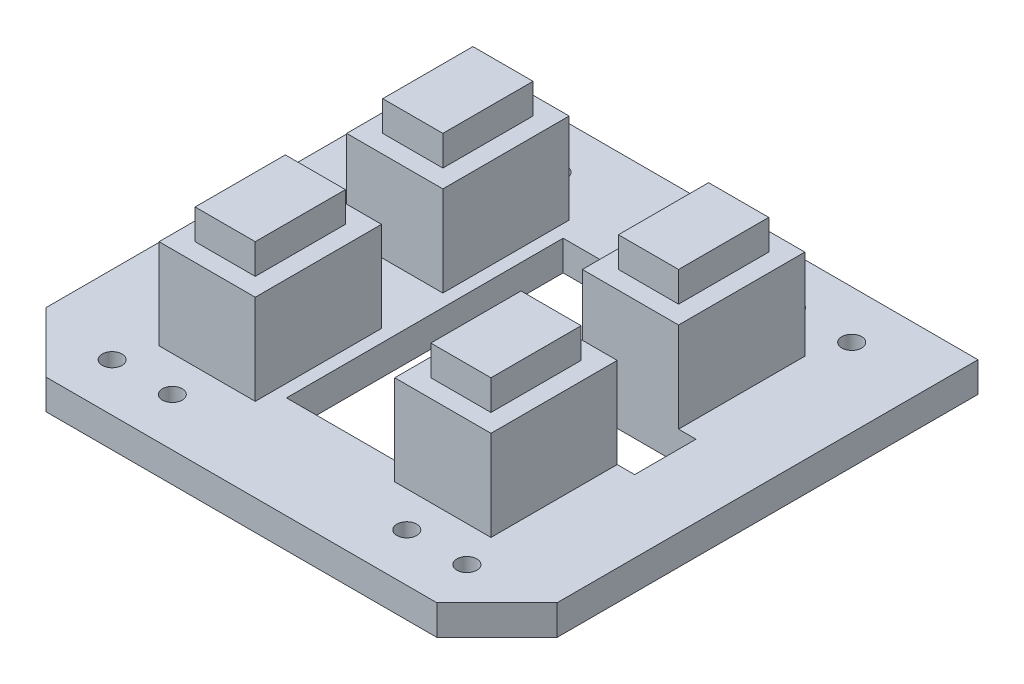
SolidWorks part; units mm, degrees
material "PLA+ esun"
ref_plane "Front Plane" through (0, 0, 0) normal (0, 0, 1) x (1, 0, 0)
ref_plane "Top Plane" through (0, 0, 0) normal (0, 1, 0) x (1, 0, 0)
ref_plane "Right Plane" through (0, 0, 0) normal (1, 0, 0) x (0, 0, -1)
sketch "Sketch1" plane through (0, 0, 0) normal (0, 1, 0) x (1, 0, 0)
  line L0 (0, 0) -> (49.8029, 0) construction
  line L1 (-77.5, 77.5) -> (77.5, 77.5)
  line L2 (-77.5, 77.5) -> (-77.5, -77.5)
  line L3 (-77.5, -77.5) -> (77.5, -77.5)
  line L4 (77.5, 77.5) -> (77.5, -77.5)
  line L5 (-77.5, 77.5) -> (77.5, -77.5) construction
  line L6 (-77.5, -77.5) -> (77.5, 77.5) construction
  line L7 (-9.5, 23) -> (9.5, 23)
  line L8 (-9.5, 23) -> (-9.5, -23)
  line L9 (-9.5, -23) -> (9.5, -23)
  line L10 (9.5, 23) -> (9.5, -23)
  line L11 (-9.5, 23) -> (9.5, -23) construction
  line L12 (-9.5, -23) -> (9.5, 23) construction
  line L14 (0, 0) -> (0, 35.7746) construction
  line L17 (-77.5, -77.5) -> (-42.5, -77.5)
  line L18 (-77.5, -77.5) -> (-77.5, -24.25)
  line L19 (-77.5, -24.25) -> (-42.5, -24.25)
  line L20 (-42.5, -77.5) -> (-42.5, -24.25)
  line L21 (-77.5, 24.25) -> (-42.5, 24.25)
  line L22 (-42.5, 77.5) -> (-42.5, 24.25)
  line L23 (42.5, -77.5) -> (42.5, -24.25)
  line L24 (77.5, -24.25) -> (42.5, -24.25)
  line L25 (42.5, 77.5) -> (42.5, 24.25)
  line L26 (77.5, 24.25) -> (42.5, 24.25)
  line L27 (20, -40) -> (42.5, -40)
  line L28 (-42.5, 24.25) -> (-77.5, 24.25)
  line L29 (-42.5, 24.25) -> (-42.5, -24.25)
  line L30 (-42.5, -24.25) -> (-77.5, -24.25)
  line L31 (-77.5, 24.25) -> (-77.5, -24.25)
  line L32 (42.5, 24.25) -> (77.5, 24.25)
  line L33 (42.5, 24.25) -> (42.5, -24.25)
  line L34 (42.5, -24.25) -> (77.5, -24.25)
  line L35 (77.5, 24.25) -> (77.5, -24.25)
  line L36 (-42.5, 77.5) -> (42.5, 77.5)
  line L37 (-42.5, 77.5) -> (-42.5, 40)
  line L38 (-42.5, 40) -> (42.5, 40)
  line L39 (42.5, 77.5) -> (42.5, 40)
  line L40 (-42.5, -77.5) -> (42.5, -77.5)
  line L41 (-42.5, -77.5) -> (-42.5, -40)
  line L42 (-42.5, -40) -> (-20, -40)
  line L43 (42.5, -77.5) -> (42.5, -40)
  line L45 (-20, -40) -> (-20, -77.5)
  line L46 (-20, -77.5) -> (20, -77.5)
  line L47 (20, -40) -> (20, -77.5)
  line L49 (-20, -77.5) -> (20, -77.5)
  line L50 (-20, -77.5) -> (-20, -40)
  line L51 (-20, -40) -> (20, -40)
  line L52 (20, -77.5) -> (20, -40)
  circle A1 centre (29.5, 32) radius 1.65
  circle A2 centre (19.5, 32) radius 1.65
  circle A3 centre (19.5, -32) radius 1.65
  circle A4 centre (29.5, -32) radius 1.65
  circle A5 centre (-29.5, -32) radius 1.65
  circle A6 centre (-19.5, -32) radius 1.65
  circle A7 centre (-19.5, 32) radius 1.65
  circle A8 centre (-29.5, 32) radius 1.65
  point P0 (0, 0)
  point P6 (0, 0)
  point P13 (0, 0)
  dimension "D5" = 9
  dimension "D8" = 20
  dimension "D9" = 53.25
  dimension "D6" = 3.3
  dimension "D1" = 155
  dimension "D2" = 155
  dimension "D3" = 46
  dimension "D4" = 19
  dimension "D7" = 2
  dimension "D10" = 35
  dimension "D11" = 37.5
  dimension "D12" = 37.5
  dimension "D13" = 22.5
  dimension "D14" = 22.5
extrude "Boss-Extrude3" add sketch "Sketch1" along normal blind 5 contours L4 L26 L25 L1 L22 L21 L2 L19 L20 L3 L23 L24 A7 A6 A5 A3 A2 A1 L7 L10 L9 L8 A4 A8 region at (0, 0, -38.8327)
chamfer "Chamfer1" distance 10 angle 45 2 edges at (-42.5, 2.5, 40) (42.5, 2.5, 40)
sketch "Sketch6" plane through (0, 5, 0) normal (0, 1, 0) x (1, 0, 0)
  line L0 (-24.6, 8.1) -> (-14.6, 8.1)
  line L9 (-14.6, 8.1) -> (-14.6, 23.1)
  line L10 (-24.6, 8.1) -> (-24.6, 23.1)
  line L11 (-24.7, 8) -> (-14.5, 8)
  line L12 (-24.7, 23.2) -> (-14.5, 23.2)
  line L13 (-24.7, 23.2) -> (-24.7, -23.2)
  line L14 (-24.7, -23.2) -> (-14.5, -23.2)
  line L15 (-14.5, 23.2) -> (-14.5, -23.2)
  line L16 (9.5, 23) -> (-9.5, 23)
  line L17 (9.5, 23) -> (9.5, -23)
  line L18 (9.5, -23) -> (-9.5, -23)
  line L19 (-9.5, 23) -> (-9.5, -23)
  line L20 (9.5, 23) -> (-9.5, -23) construction
  line L21 (9.5, -23) -> (-9.5, 23) construction
  line L22 (-24.7, -8) -> (-14.5, -8)
  line L23 (0, 0) -> (0, -14.0514) construction
  line L24 (24.6, 23.1) -> (14.6, 23.1)
  line L29 (14.6, -8.1) -> (14.6, -23.1)
  line L30 (0, 0) -> (7.1407, 0) construction
  line L35 (-24.6, -8.1) -> (-14.6, -8.1)
  line L36 (-24.6, -8.1) -> (-24.6, -23.1)
  line L37 (-24.6, -23.1) -> (-14.6, -23.1)
  line L38 (-14.6, -8.1) -> (-14.6, -23.1)
  line L39 (-24.6, 23.1) -> (-14.6, 23.1)
  line L40 (24.6, -23.1) -> (14.6, -23.1)
  line L41 (24.6, -8.1) -> (24.6, -23.1)
  line L42 (24.6, -8.1) -> (14.6, -8.1)
  line L43 (24.7, -8) -> (14.5, -8)
  line L44 (14.5, 23.2) -> (14.5, -23.2)
  line L45 (24.7, -23.2) -> (14.5, -23.2)
  line L46 (24.7, 23.2) -> (24.7, -23.2)
  line L47 (24.7, 23.2) -> (14.5, 23.2)
  line L48 (24.7, 8) -> (14.5, 8)
  line L49 (24.6, 8.1) -> (24.6, 23.1)
  line L50 (14.6, 8.1) -> (14.6, 23.1)
  line L51 (24.6, 8.1) -> (14.6, 8.1)
  point P4 (0, 0)
  dimension "D1" = 0.2
  dimension "D2" = 5
  dimension "D3" = 0.2
  dimension "D4" = 10.2
  dimension "D5" = 15.2
  dimension "D6" = 15.2
  dimension "D7" = 0.1
  dimension "D8" = 0.1
  dimension "D9" = 0.1
  dimension "D10" = 0.1
extrude "Boss-Extrude4" add sketch "Sketch6" along normal blind 20 contours L51 L49 L24 L50 | L39 L10 L0 L9 | L38 L35 L36 L37 | L41 L42 L29 L40 region at (-19.6, 5, -15.6) region at (19.6, 5, -15.6) region at (19.6, 5, 15.6) region at (-19.6, 5, 15.6)
sketch "Sketch8" plane through (0, 5, 0) normal (0, 1, 0) x (1, 0, 0)
  line L0 (0, 0) -> (0, -16.476) construction
  line L1 (-27.6, 26.1) -> (-11.6, 26.1)
  line L2 (-27.6, 26.1) -> (-27.6, -26.1)
  line L3 (-27.6, -26.1) -> (-11.6, -26.1)
  line L4 (-11.6, 26.1) -> (-11.6, -26.1)
  line L5 (-24.6, 23.1) -> (-14.6, 23.1) construction
  line L6 (-24.6, 8.1) -> (-24.6, 23.1) construction
  line L7 (-14.6, 8.1) -> (-14.6, 23.1) construction
  line L8 (-24.6, -23.1) -> (-14.6, -23.1) construction
  line L9 (11.6, 26.1) -> (11.6, -26.1)
  line L10 (27.6, -26.1) -> (11.6, -26.1)
  line L11 (27.6, 26.1) -> (27.6, -26.1)
  line L12 (27.6, 26.1) -> (11.6, 26.1)
  line L13 (-24.6, 8.1) -> (-14.6, 8.1) construction
  line L14 (-27.6, 5.1) -> (-11.6, 5.1)
  line L15 (-27.6, 5.1) -> (-27.6, -5.1)
  line L16 (-27.6, -5.1) -> (-11.6, -5.1)
  line L17 (-11.6, 5.1) -> (-11.6, -5.1)
  line L18 (-24.6, -8.1) -> (-14.6, -8.1) construction
  line L19 (27.6, -5.1) -> (11.6, -5.1)
  line L20 (27.6, 5.1) -> (11.6, 5.1)
  line M8 (24.6, -8.1) -> (24.6, -23.1)
  line M9 (24.6, -23.1) -> (14.6, -23.1)
  line M10 (14.6, -23.1) -> (14.6, -8.1)
  line M11 (14.6, -8.1) -> (24.6, -8.1)
  line M12 (-14.6, -8.1) -> (-14.6, -23.1)
  line M13 (-14.6, -23.1) -> (-24.6, -23.1)
  line M14 (-24.6, -23.1) -> (-24.6, -8.1)
  line M15 (-24.6, -8.1) -> (-14.6, -8.1)
  line M16 (-24.6, 23.1) -> (-14.6, 23.1)
  line M17 (-14.6, 23.1) -> (-14.6, 8.1)
  line M18 (-14.6, 8.1) -> (-24.6, 8.1)
  line M19 (-24.6, 8.1) -> (-24.6, 23.1)
  line M20 (24.6, 8.1) -> (14.6, 8.1)
  line M21 (14.6, 8.1) -> (14.6, 23.1)
  line M22 (14.6, 23.1) -> (24.6, 23.1)
  line M23 (24.6, 23.1) -> (24.6, 8.1)
  dimension "D1" = 3
  dimension "D2" = 3
  dimension "D3" = 3
  dimension "D4" = 3
  dimension "D5" = 3
  dimension "D6" = 3
extrude "Boss-Extrude5" add sketch "Sketch8" along normal blind 15 contours L2 L14 L4 L1 M19 M16 M17 M18 | L16 L2 L3 L4 M15 M12 M13 M14 | L11 L19 L9 L10 M11 M8 M9 M10 | L20 L11 L12 L9 M23 M20 M21 M22 region at (-19.6, 5, -25.836) region at (-19.6, 5, 5.364) region at (19.6, 5, -25.836) region at (19.6, 5, 5.364)
sketch "Sketch5" plane through (0, 0, 0) normal (0, -1, 0) x (1, 0, 0)
  line L0 (9.5, -23) -> (9.5, 23) construction
  line L1 (14.5, 5.1) -> (30.5, 5.1)
  line L2 (14.5, 5.1) -> (14.5, -5.1)
  line L3 (14.5, -5.1) -> (30.5, -5.1)
  line L4 (30.5, 5.1) -> (30.5, -5.1)
  line L5 (-9.5, -23) -> (9.5, -23) construction
  line L6 (-9.5, 23) -> (9.5, 23) construction
  dimension "D1" = 5
  dimension "D2" = 16
  dimension "D3" = 17.9
  dimension "D4" = 17.9
extrude "Cut-Extrude1" cut sketch "Sketch5" against normal through all
